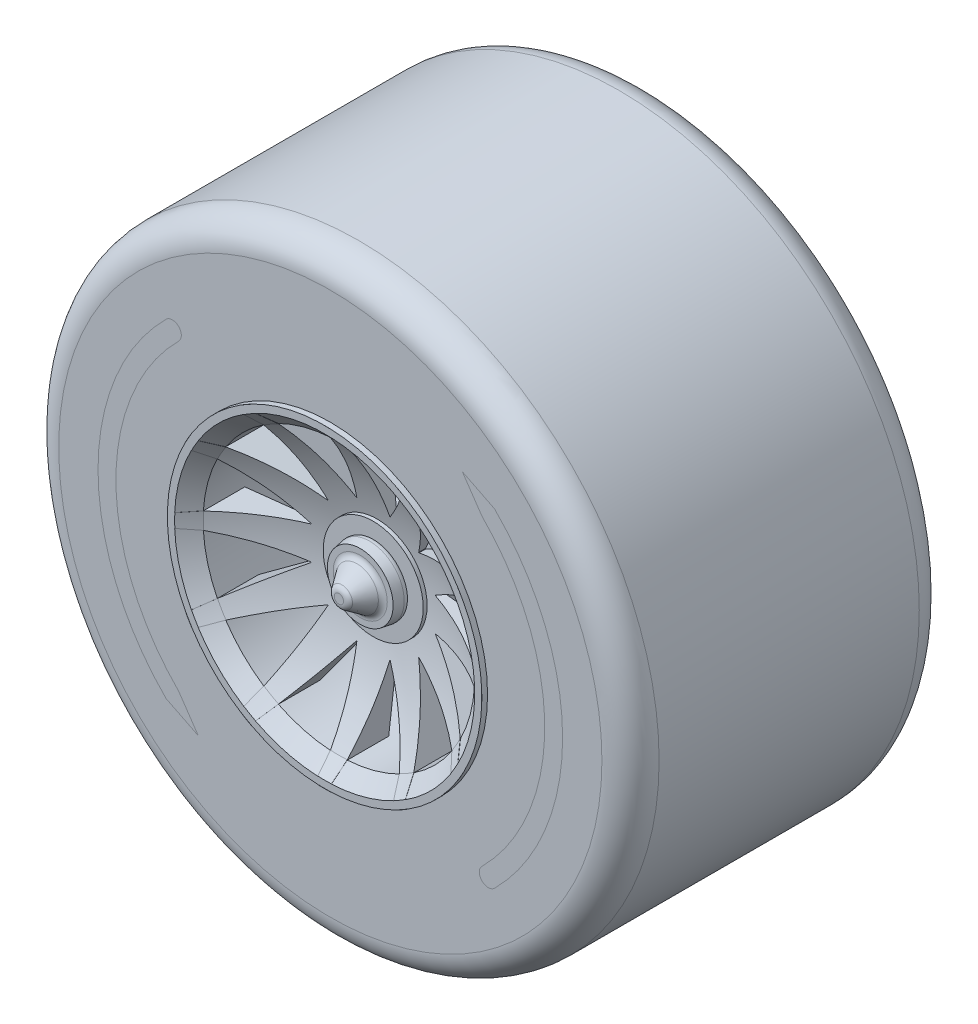
SolidWorks part; units mm, degrees
ref_plane "Front Plane" through (0, 0, 0) normal (0, 0, 1) x (1, 0, 0)
ref_plane "Top Plane" through (0, 0, 0) normal (0, 1, 0) x (1, 0, 0)
ref_plane "Right Plane" through (0, 0, 0) normal (1, 0, 0) x (0, 0, -1)
sketch "Sketch1" plane through (0, 0, 0) normal (1, 0, 0) x (0, 0, -1)
  line L0 (0, 0) -> (0, 21)
  line L1 (0, 21) -> (-9.1, 21)
  line L2 (-11.1, 19) -> (-11.1, 11)
  line L3 (-11.1, 11) -> (-11.5, 11)
  line L4 (-11.5, 11) -> (-11.5, 0)
  line L5 (-11.5, 0) -> (0, 0)
  arc A0 (-9.1, 21) -> (-11.1, 19) centre (-9.1, 19) ccw
  dimension "D5" = 2
  dimension "D1" = 21
  dimension "D2" = 0.4
  dimension "D3" = 11
  dimension "D4" = 11.5
revolve "Revolve1" add sketch "Sketch1" angle 360 about L5
sketch "Sketch2" plane through (0, 0, 0) normal (0, 0, 1) x (1, 0, 0)
  circle A0 centre (0, 0) radius 9.5
  dimension "D1" = 19
extrude "Cut-Extrude1" cut sketch "Sketch2" along normal blind 24
chamfer "Chamfer1" distance 1 angle 45 1 edges at (-9.5, 0, 11.5)
sketch "Sketch3" plane through (0, 0, 11.1) normal (0, 0, 1) x (1, 0, 0)
  line L0 (0, 0) -> (0, 18.0694) construction
  line L1 (-0.4205, 10.992) -> (-1.1507, 4.3504)
  line L2 (0.4205, 10.992) -> (1.1507, 4.3504)
  line L3 (5.1318, 9.7296) -> (1.1786, 4.3429)
  line L4 (5.8602, 9.3091) -> (3.1718, 3.1922)
  line L5 (9.3091, 5.8602) -> (3.1922, 3.1718)
  line L6 (9.7296, 5.1318) -> (4.3429, 1.1786)
  line L7 (10.992, 0.4205) -> (4.3504, 1.1507)
  line L8 (10.992, -0.4205) -> (4.3504, -1.1507)
  line L9 (9.7296, -5.1318) -> (4.3429, -1.1786)
  line L10 (9.3091, -5.8602) -> (3.1922, -3.1718)
  line L11 (5.8602, -9.3091) -> (3.1718, -3.1922)
  line L12 (5.1318, -9.7296) -> (1.1786, -4.3429)
  line L13 (0.4205, -10.992) -> (1.1507, -4.3504)
  line L14 (-0.4205, -10.992) -> (-1.1507, -4.3504)
  line L15 (-5.1318, -9.7296) -> (-1.1786, -4.3429)
  line L16 (-5.8602, -9.3091) -> (-3.1718, -3.1922)
  line L17 (-9.3091, -5.8602) -> (-3.1922, -3.1718)
  line L18 (-9.7296, -5.1318) -> (-4.3429, -1.1786)
  line L19 (-10.992, -0.4205) -> (-4.3504, -1.1507)
  line L20 (-10.992, 0.4205) -> (-4.3504, 1.1507)
  line L21 (-9.7296, 5.1318) -> (-4.3429, 1.1786)
  line L22 (-9.3091, 5.8602) -> (-3.1922, 3.1718)
  line L23 (-5.8602, 9.3091) -> (-3.1718, 3.1922)
  line L24 (-5.1318, 9.7296) -> (-1.1786, 4.3429)
  arc A0 (-9.3091, 5.8602) -> (-9.7296, 5.1318) centre (0, 0) ccw
  arc A1 (-3.1718, 3.1922) -> (-3.1922, 3.1718) centre (0, 0) ccw
  arc A2 (-5.1318, 9.7296) -> (-5.8602, 9.3091) centre (0, 0) ccw
  arc A3 (0.4205, 10.992) -> (-0.4205, 10.992) centre (0, 0) ccw
  arc A4 (5.8602, 9.3091) -> (5.1318, 9.7296) centre (0, 0) ccw
  arc A5 (9.7296, 5.1318) -> (9.3091, 5.8602) centre (0, 0) ccw
  arc A6 (10.992, -0.4205) -> (10.992, 0.4205) centre (0, 0) ccw
  arc A7 (9.3091, -5.8602) -> (9.7296, -5.1318) centre (0, 0) ccw
  arc A8 (5.1318, -9.7296) -> (5.8602, -9.3091) centre (0, 0) ccw
  arc A9 (-0.4205, -10.992) -> (0.4205, -10.992) centre (0, 0) ccw
  arc A10 (-5.8602, -9.3091) -> (-5.1318, -9.7296) centre (0, 0) ccw
  arc A11 (-9.7296, -5.1318) -> (-9.3091, -5.8602) centre (0, 0) ccw
  arc A12 (-10.992, 0.4205) -> (-10.992, -0.4205) centre (0, 0) ccw
  arc A13 (-1.1507, 4.3504) -> (-1.1786, 4.3429) centre (0, 0) ccw
  arc A14 (1.1786, 4.3429) -> (1.1507, 4.3504) centre (0, 0) ccw
  arc A15 (3.1922, 3.1718) -> (3.1718, 3.1922) centre (0, 0) ccw
  arc A16 (4.3504, 1.1507) -> (4.3429, 1.1786) centre (0, 0) ccw
  arc A17 (4.3429, -1.1786) -> (4.3504, -1.1507) centre (0, 0) ccw
  arc A18 (3.1718, -3.1922) -> (3.1922, -3.1718) centre (0, 0) ccw
  arc A19 (1.1507, -4.3504) -> (1.1786, -4.3429) centre (0, 0) ccw
  arc A20 (-1.1786, -4.3429) -> (-1.1507, -4.3504) centre (0, 0) ccw
  arc A21 (-3.1922, -3.1718) -> (-3.1718, -3.1922) centre (0, 0) ccw
  arc A22 (-4.3504, -1.1507) -> (-4.3429, -1.1786) centre (0, 0) ccw
  arc A23 (-4.3429, 1.1786) -> (-4.3504, 1.1507) centre (0, 0) ccw
  point P56 (0, 0)
  dimension "D1" = 22
  dimension "D2" = 9
  dimension "D3" = 12
extrude "Boss-Extrude1" add sketch "Sketch3" along normal blind 10 and the other way blind 3.5
sketch "Sketch4" plane through (0, 0, 0) normal (1, 0, 0) x (0, 0, -1)
  line L0 (-7.3499, 0) -> (-21.6501, 0)
  line L1 (-10.5, 9.4819) -> (-11.5, 10.4892)
  line L2 (-11.5, 10.4892) -> (-11.5, 10.992)
  line L3 (-11.5, 10.992) -> (-11.8492, 11.6077)
  line L4 (-11.8492, 11.6077) -> (-21.6501, 11.6077)
  line L5 (-21.6501, 11.6077) -> (-21.6501, 0)
  spline S0 degree 2 poles (-10.5, 9.4819) (-7.6216, 5.4234) (-7.3499, 0) knots 0 0 0 1 1 1
revolve "Cut-Revolve1" cut sketch "Sketch4" angle 360 about L0
sketch "Sketch5" plane through (0, 0, 0) normal (1, 0, 0) x (0, 0, -1)
  line L0 (0, 0) -> (-15.7493, 0) construction
  line L1 (-7.8663, 2.5) -> (-7.3803, 0)
  line L2 (0, 0) -> (-9.1, 0) construction
  line L3 (-7.8663, 2.5) -> (-9.0069, 2.3009)
  line L5 (-10.5, 0.5865) -> (-10.5, 0)
  line L6 (-10.5, 0.5886) -> (-10.5, -0.5886) construction
  line L7 (-10.5, 0) -> (-7.3803, 0)
  line L8 (-9.0069, 2.3009) -> (-9.0069, 1.6294)
  line L9 (-9.0069, 1.6294) -> (-10.5, 0.5865)
  dimension "D1" = 2.5
  dimension "D2" = 101
revolve "Revolve2" add sketch "Sketch5" angle 360 about L0
fillet "Fillet1" radius 0.5 3 edges at (-2.5, 0, 7.8663) (-1.6294, 0, 9.0069) (-0.5865, 0, 10.5)
mirror "Mirror1" about plane through (0, 0, 0) normal (0, 0, 1) of bodies 104 105
sketch "Sketch6" plane through (0, 0, 11.1) normal (0, 0, 1) x (1, 0, 0)
  circle A0 centre (0, 0) radius 3.5
  dimension "D1" = 7
extrude "Boss-Extrude2" add sketch "Sketch6" against normal blind 15 from offset 3 offset against normal yes
sketch "Sketch7" plane through (0, 0, -11.1) normal (0, 0, -1) x (-1, 0, 0)
  circle A0 centre (0, 0) radius 2.55
  dimension "D1" = 5.1
extrude "Cut-Extrude2" cut sketch "Sketch7" against normal blind 5
sketch "Sketch8" plane through (0, 0, 11.1) normal (0, 0, 1) x (1, 0, 0)
  line L1 (0, 0) -> (0, 16.25) construction
  line L4 (11.4905, 11.4905) -> (9.2319, 12.6214)
  line L5 (9.2319, 12.6214) -> (10.6066, 10.6066)
  line L6 (-10.6066, -10.6066) -> (-9.2366, -12.6145)
  line L7 (-9.2366, -12.6145) -> (-11.4905, -11.4905)
  arc A0 (-10.6066, 10.6066) -> (-10.6066, -10.6066) centre (0, 0) ccw
  arc A1 (-11.4905, 11.4905) -> (-11.4905, -11.4905) centre (0, 0) ccw
  circle A2 centre (0, 0) radius 16.25 construction
  circle A3 centre (0, 0) radius 15 construction
  arc A4 (10.6066, -10.6066) -> (10.6066, 10.6066) centre (0, 0) ccw
  arc A5 (11.4905, -11.4905) -> (11.4905, 11.4905) centre (0, 0) ccw
  arc A6 (-10.6066, 10.6066) -> (-11.4905, 11.4905) centre (-11.0485, 11.0485) ccw
  arc A7 (11.4905, -11.4905) -> (10.6066, -10.6066) centre (11.0485, -11.0485) cw
  dimension "D1" = 30
  dimension "D2" = 1.25
split line "Split Line1"
